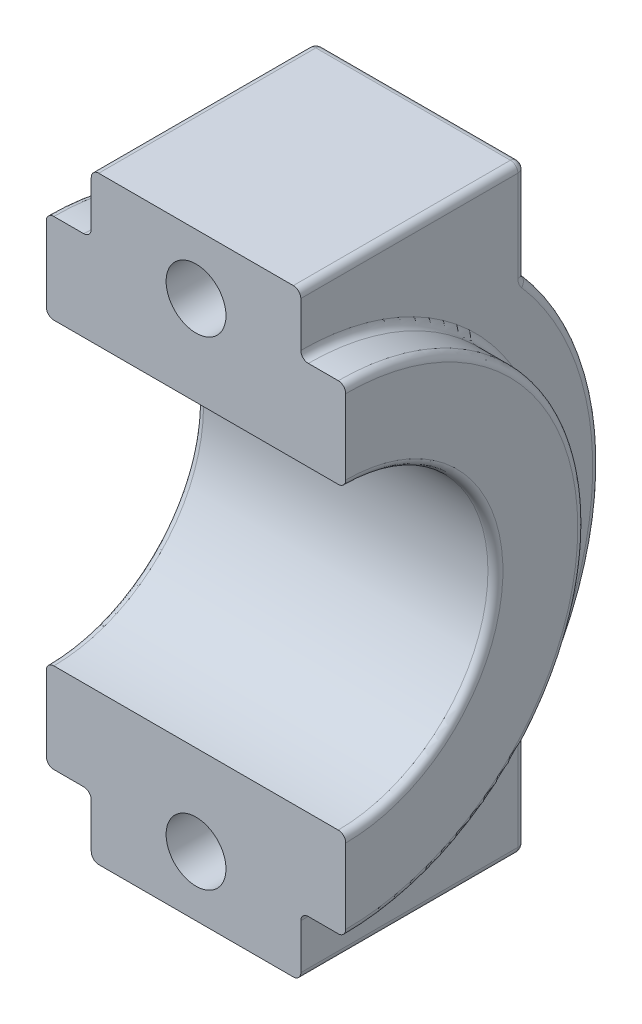
SolidWorks part; units mm, degrees
material "AISI 4340 Steel, normalized"
ref_plane "Front Plane" through (0, 0, 0) normal (1, 0, 0) x (0, 1, 0)
ref_plane "Top Plane" through (0, 0, 0) normal (0, 0, 1) x (0, 1, 0)
ref_plane "Right Plane" through (0, 0, 0) normal (0, 1, 0) x (-1, 0, 0)
sketch "Sketch1" plane through (0, 0, 0) normal (1, 0, 0) x (0, 1, 0)
  line L0 (0, 7.5) -> (0, -16.7882) construction
  line L1 (-20, 7.5) -> (20, 7.5)
  line L2 (-20, 7.5) -> (-20, -7.5)
  line L3 (-20, -7.5) -> (-13.2288, -7.5)
  line L4 (20, 7.5) -> (20, -7.5)
  line L5 (-20, 7.5) -> (20, -7.5) construction
  line L6 (-20, -7.5) -> (20, 7.5) construction
  line L7 (13.2288, -7.5) -> (20, -7.5)
  arc A0 (-10, 7.5) -> (10, 7.5) centre (0, 7.5) ccw
  arc A1 (-16, 7.5) -> (16, 7.5) centre (0, 7.5) ccw
  arc A2 (-13.2288, -7.5) -> (13.2288, -7.5) centre (0, 7.5) ccw
  point P0 (0, 0)
  point P18 (0, -8.5)
  point P19 (0, -2.5)
  point P20 (0, -12.5)
  dimension "D3" = 20
  dimension "D4" = 16
  dimension "D5" = 10
  dimension "D1" = 15
  dimension "D2" = 40
  dimension "D6" = 20
extrude "Boss-Extrude1" add sketch "Sketch1" along normal mid plane 20 contours L1 A1 A0 region at (0, -13, 7.1422)
extrude "Boss-Extrude2" add sketch "Sketch1<3>" along normal mid plane 14 contours L3 A2 L7 L4 L1 A1 L2 region at (0, -18, 7.0528)
sketch "Sketch1<3>" plane through (0, 0, 0) normal (1, 0, 0) x (0, 1, 0) same geometry as "Sketch1"
sketch "Sketch2" plane through (0, 0, 7.5) normal (0, 0, 1) x (1, 0, 0)
  line L0 (-3.3101, 0) -> (3.4756, 0) construction
  circle A0 centre (0, 16) radius 2
  circle A1 centre (0, -16) radius 2
  dimension "D1" = 4
  dimension "D2" = 32
extrude "Cut-Extrude1" cut sketch "Sketch2" against normal blind 15
fillet "Fillet1" radius 0.5 20 edges at (-7, 0, -12.5) (0, 13.2288, -7.5) (-7, 16.6144, -7.5) (0, -13.2288, -7.5) (7, 0, -12.5) (-7, -16.6144, -7.5) (0, 20, -7.5) (7, 16.6144, -7.5) (-7, 20, 0) (7, -16.6144, -7.5) (0, -20, -7.5) (-7, -20, 0) (7, 20, 0) (7, -20, 0) (-7, 0, -8.5) (7, 0, -8.5) (-10, 0, -8.5) (10, 0, -8.5) (-10, 0, -2.5) (10, 0, -2.5)
